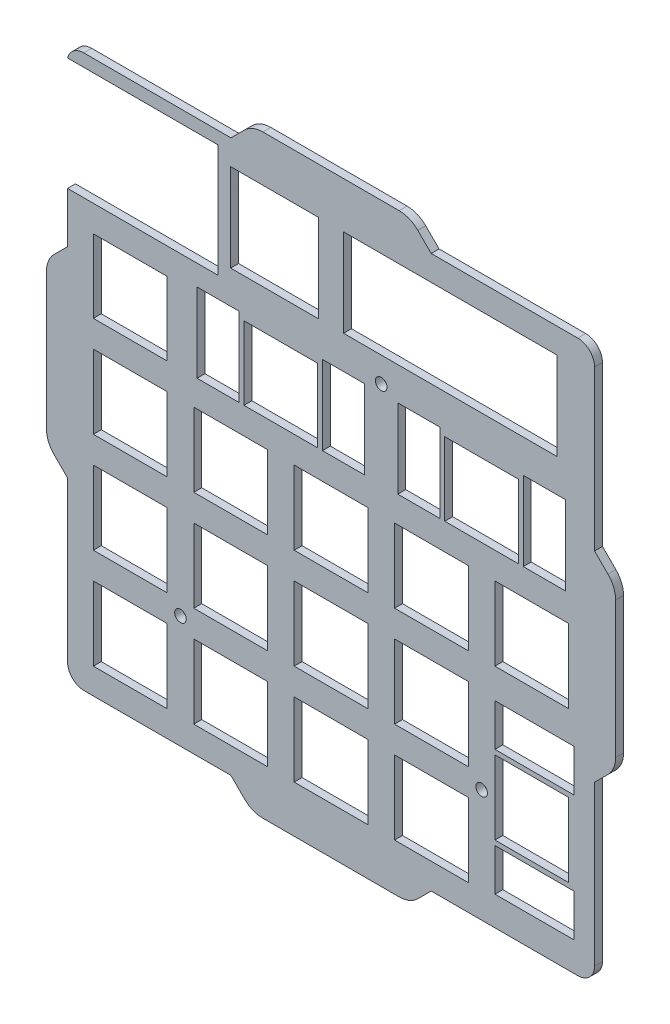
SolidWorks part; units mm, degrees
ref_plane "Front Plane" through (0, 0, 0) normal (1, 0, 0) x (0, 1, 0)
ref_plane "Top Plane" through (0, 0, 0) normal (0, 0, 1) x (0, 1, 0)
ref_plane "Right Plane" through (0, 0, 0) normal (0, 1, 0) x (-1, 0, 0)
sketch "Sketch2" plane through (0, 0, 0) normal (0, 0, 1) x (0, 1, 0)
  line L0 (0.0954, 95.5094) -> (76.2988, 95.5094) construction
  line L1 (76.2988, 95.5094) -> (76.2988, 76.4594) construction
  line L2 (76.2988, 0.2594) -> (0.0954, 0.2594) construction
  line L3 (0.0954, 0.2594) -> (0.0954, 95.5094) construction
  line L20 (12.1454, 16.7838) -> (12.1454, 2.7838)
  line L21 (12.1454, 2.7838) -> (26.1454, 2.7838)
  line L22 (26.1454, 2.7838) -> (26.1454, 16.7838)
  line L39 (26.1454, 16.7838) -> (12.1454, 16.7838)
  line L40 (40.7217, 16.7838) -> (54.7216, 16.7838)
  line L41 (54.7216, 16.7838) -> (54.7216, 2.7838)
  line L42 (54.7216, 2.7838) -> (40.7217, 2.7838)
  line L43 (40.7217, 2.7838) -> (40.7217, 16.7838)
  line L54 (59.7727, 26.3094) -> (59.7727, 12.3094)
  line L71 (59.7727, 12.3094) -> (73.6711, 12.3094)
  line L72 (73.6711, 12.3094) -> (73.6711, 26.3094)
  line L73 (73.6711, 26.3094) -> (59.7727, 26.3094)
  line L80 (2.6198, 35.8339) -> (16.62, 35.8339)
  line L81 (16.62, 35.8339) -> (16.62, 21.8347)
  line L82 (16.62, 21.8347) -> (2.6198, 21.8347)
  line L83 (2.6198, 21.8347) -> (2.6198, 35.8339)
  line L84 (21.6708, 35.8339) -> (35.6708, 35.8339)
  line L85 (35.6708, 35.8339) -> (35.6708, 21.8347)
  line L86 (35.6708, 21.8347) -> (21.6708, 21.8347)
  line L87 (21.6708, 21.8347) -> (21.6708, 35.8339)
  line L88 (40.7217, 35.8339) -> (54.7216, 35.8339)
  line L89 (54.7216, 35.8339) -> (54.7216, 21.8347)
  line L90 (54.7216, 21.8347) -> (40.7217, 21.8347)
  line L91 (40.7217, 21.8347) -> (40.7217, 35.8339)
  line L92 (2.6198, 54.8839) -> (16.62, 54.8839)
  line L93 (16.62, 54.8839) -> (16.62, 40.8849)
  line L94 (16.62, 40.8849) -> (2.6198, 40.8849)
  line L95 (2.6198, 40.8849) -> (2.6198, 54.8839)
  line L96 (21.6708, 54.8839) -> (35.6708, 54.8839)
  line L97 (35.6708, 54.8839) -> (35.6708, 40.8849)
  line L98 (35.6708, 40.8849) -> (21.6708, 40.8849)
  line L99 (21.6708, 40.8849) -> (21.6708, 54.8839)
  line L100 (40.7217, 54.8839) -> (54.7216, 54.8839)
  line L101 (54.7216, 54.8839) -> (54.7216, 40.8849)
  line L102 (54.7216, 40.8849) -> (40.7217, 40.8849)
  line L103 (40.7217, 40.8849) -> (40.7217, 54.8839)
  line L114 (59.7727, 64.4094) -> (59.7727, 50.4094)
  line L131 (59.7727, 50.4094) -> (73.6711, 50.4094)
  line L132 (73.6711, 50.4094) -> (73.6711, 64.4094)
  line L133 (73.6711, 64.4094) -> (59.7727, 64.4094)
  line L140 (2.6198, 73.9309) -> (16.62, 73.9309)
  line L141 (16.62, 73.9309) -> (16.62, 59.9368)
  line L142 (16.62, 59.9368) -> (2.6198, 59.9368)
  line L143 (2.6198, 59.9368) -> (2.6198, 73.9309)
  line L144 (21.6708, 73.9309) -> (35.6708, 73.9309)
  line L145 (35.6708, 73.9309) -> (35.6708, 59.9368)
  line L146 (35.6708, 59.9368) -> (21.6708, 59.9368)
  line L147 (21.6708, 59.9368) -> (21.6708, 73.9309)
  line L148 (40.7217, 73.9309) -> (54.7216, 73.9309)
  line L149 (54.7216, 73.9309) -> (54.7216, 59.9368)
  line L150 (54.7216, 59.9368) -> (40.7217, 59.9368)
  line L151 (40.7217, 59.9368) -> (40.7217, 73.9309)
  line L152 (2.6198, 92.9878) -> (16.62, 92.9878)
  line L153 (16.62, 92.9878) -> (16.62, 78.9878)
  line L154 (16.62, 78.9878) -> (2.6198, 78.9878)
  line L155 (2.6198, 78.9878) -> (2.6198, 92.9878)
  line L156 (21.6708, 92.9878) -> (35.6708, 92.9878)
  line L157 (35.6708, 92.9878) -> (35.6708, 78.9878)
  line L158 (35.6708, 78.9878) -> (21.6708, 78.9878)
  line L159 (21.6708, 78.9878) -> (21.6708, 92.9878)
  line L160 (40.7217, 92.9878) -> (54.7216, 92.9878)
  line L161 (54.7216, 92.9878) -> (54.7216, 78.9878)
  line L162 (54.7216, 78.9878) -> (40.7217, 78.9878)
  line L163 (40.7217, 78.9878) -> (40.7217, 92.9878)
  line L164 (59.7727, 92.9878) -> (73.6711, 92.9878)
  line L165 (73.6711, 92.9878) -> (73.6711, 78.9878)
  line L166 (73.6711, 78.9878) -> (59.7727, 78.9878)
  line L167 (59.7727, 78.9878) -> (59.7727, 92.9878)
  line L168 (76.2988, 95.5094) -> (102.4915, 95.5094) construction
  line L169 (76.2988, 0.2594) -> (102.4915, 0.2594) construction
  line L170 (102.4915, 0.2594) -> (102.4915, 95.5094) construction
  line L172 (19.1454, 95.5094) -> (19.1454, 0.2594) construction
  line L173 (0.0954, 76.4594) -> (76.2988, 76.4594) construction
  line L174 (0.0954, 57.4094) -> (76.2988, 57.4094) construction
  line L175 (0.0954, 38.3594) -> (76.2988, 38.3594) construction
  line L176 (0.0954, 19.3094) -> (76.2988, 19.3094) construction
  line L177 (38.1971, 95.5094) -> (38.1971, 0.2594) construction
  line L178 (57.2471, 95.5094) -> (57.2471, 0.2594) construction
  line L179 (76.2988, 45.5031) -> (81.0613, 45.5031) construction
  line L180 (81.0613, 66.9344) -> (97.73, 66.9344)
  line L181 (81.0613, 66.9344) -> (81.0613, 50.2656)
  line L182 (81.0613, 50.2656) -> (97.73, 50.2656)
  line L183 (97.73, 66.9344) -> (97.73, 50.2656)
  line L184 (81.0613, 45.5031) -> (81.0613, 5.0219)
  line L185 (81.0613, 5.0219) -> (97.73, 5.0219)
  line L186 (97.73, 5.0219) -> (97.73, 45.5031)
  line L187 (97.73, 45.5031) -> (81.0613, 45.5031)
  line L189 (78.68, 95.5094) -> (78.68, 69.3156)
  line L190 (78.68, 69.3156) -> (100.1103, 69.3156)
  line L191 (100.1103, 95.5636) -> (100.1103, 69.3156)
  line L194 (102.4915, 0.2594) -> (102.4915, 28.8844)
  line L195 (102.4915, 0.2594) -> (102.4915, -2.1219)
  line L196 (102.4915, -2.1219) -> (69.1029, -2.1219)
  line L197 (-2.2858, -2.1219) -> (-2.2858, 28.8844)
  line L198 (-2.2858, 97.8906) -> (31.1029, 97.8906)
  line L199 (78.68, 97.8906) -> (78.68, 95.5094)
  line L200 (100.1103, 95.5636) -> (100.1103, 97.8906)
  line L201 (100.1103, 97.8906) -> (102.4915, 97.8906)
  line L202 (102.4915, 97.8906) -> (102.4915, 95.5094)
  line L203 (35.0454, 1.7838) -> (27.0454, 1.7838)
  line L204 (3.2454, 16.7838) -> (11.2454, 16.7838)
  line L205 (3.2454, 16.7838) -> (3.2454, 1.7838)
  line L206 (3.2454, 1.7838) -> (11.2454, 1.7838)
  line L207 (11.2454, 16.7838) -> (11.2454, 1.7838)
  line L208 (27.0454, 16.7838) -> (27.0454, 1.7838)
  line L209 (35.0454, 16.7838) -> (27.0454, 16.7838)
  line L210 (35.0454, 16.7838) -> (35.0454, 1.7838)
  line L211 (59.7727, 35.2094) -> (74.7727, 35.2094)
  line L212 (59.7727, 11.4094) -> (74.7727, 11.4094)
  line L213 (59.7727, 11.4094) -> (59.7727, 3.4094)
  line L214 (59.7727, 3.4094) -> (74.7727, 3.4094)
  line L215 (74.7727, 11.4094) -> (74.7727, 3.4094)
  line L216 (74.7727, 27.2094) -> (74.7727, 35.2094)
  line L217 (59.7727, 27.2094) -> (74.7727, 27.2094)
  line L218 (59.7727, 27.2094) -> (59.7727, 35.2094)
  line L219 (59.7727, 41.5094) -> (74.7727, 41.5094)
  line L220 (59.7727, 65.3094) -> (74.7727, 65.3094)
  line L221 (59.7727, 65.3094) -> (59.7727, 73.3094)
  line L222 (59.7727, 73.3094) -> (74.7727, 73.3094)
  line L223 (74.7727, 65.3094) -> (74.7727, 73.3094)
  line L224 (74.7727, 49.5094) -> (74.7727, 41.5094)
  line L225 (59.7727, 49.5094) -> (74.7727, 49.5094)
  line L226 (59.7727, 49.5094) -> (59.7727, 41.5094)
  line L227 (7.2454, 16.7838) -> (19.1454, 16.7838) construction
  line L228 (59.7727, 7.4094) -> (59.7727, 19.3094) construction
  line L229 (59.7727, 57.4094) -> (59.7727, 69.3094) construction
  line L230 (76.2988, 38.3594) -> (76.2988, 0.2594) construction
  line L231 (76.2988, 76.4594) -> (76.2988, 38.3594) construction
  line L232 (50.1029, -2.1219) -> (50.1029, -6.1219) construction
  line L233 (63.0318, -6.1219) -> (37.1739, -6.1219)
  line L234 (66.5673, -4.6574) -> (69.1029, -2.1219)
  line L235 (33.6384, -4.6574) -> (31.1029, -2.1219)
  line L236 (31.1029, -2.1219) -> (-2.2858, -2.1219)
  line L237 (69.1029, -2.1219) -> (31.1029, -2.1219) construction
  line L238 (-2.2858, 47.8844) -> (102.4915, 47.8844) construction
  line L239 (50.1029, -2.1219) -> (50.1029, 97.8906) construction
  line L240 (50.1029, 97.8906) -> (50.1029, 101.8906) construction
  line L244 (31.1029, 97.8906) -> (69.1029, 97.8906) construction
  line L245 (69.1029, 97.8906) -> (78.68, 97.8906)
  line L246 (37.1739, 101.8906) -> (63.0318, 101.8906)
  line L247 (66.5673, 100.4261) -> (69.1029, 97.8906)
  line L248 (31.1029, 97.8906) -> (33.6384, 100.4261)
  line L249 (-2.2858, 47.8844) -> (-6.2858, 47.8844) construction
  line L250 (-6.2858, 60.8133) -> (-6.2858, 34.9554)
  line L251 (-4.8214, 31.4199) -> (-2.2858, 28.8844)
  line L252 (-4.8214, 64.3488) -> (-2.2858, 66.8844)
  line L253 (-2.2858, 28.8844) -> (-2.2858, 66.8844) construction
  line L254 (-2.2858, 66.8844) -> (-2.2858, 97.8906)
  line L255 (102.4915, 47.8844) -> (106.4915, 47.8844) construction
  line L256 (106.4915, 60.8133) -> (106.4915, 34.9554)
  line L257 (105.0271, 64.3488) -> (102.4915, 66.8844)
  line L258 (102.4915, 66.8844) -> (102.4915, 95.5094)
  line L260 (105.0271, 31.4199) -> (102.4915, 28.8844)
  arc A0 (-6.2858, 34.9554) -> (-4.8214, 31.4199) centre (-1.2858, 34.9554) ccw
  arc A1 (-6.2858, 60.8133) -> (-4.8214, 64.3488) centre (-1.2858, 60.8133) cw
  arc A2 (37.1739, 101.8906) -> (33.6384, 100.4261) centre (37.1739, 96.8906) ccw
  arc A3 (63.0318, 101.8906) -> (66.5673, 100.4261) centre (63.0318, 96.8906) cw
  arc A4 (106.4915, 60.8133) -> (105.0271, 64.3488) centre (101.4915, 60.8133) ccw
  arc A5 (106.4915, 34.9554) -> (105.0271, 31.4199) centre (101.4915, 34.9554) cw
  arc A6 (37.1739, -6.1219) -> (33.6384, -4.6574) centre (37.1739, -1.1219) cw
  arc A7 (63.0318, -6.1219) -> (66.5673, -4.6574) centre (63.0318, -1.1219) ccw
  circle A8 centre (19.1454, 76.4594) radius 1.1
  circle A9 centre (19.1454, 19.3094) radius 1.1
  circle A10 centre (76.2988, 38.3594) radius 1.1
  point P11 (19.1454, 16.7838)
  point P36 (7.2454, 16.7838)
  point P38 (59.7727, 19.3094)
  point P39 (59.7727, 7.4094)
  point P40 (59.7727, 69.3094)
  point P41 (59.7727, 57.4094)
  point P55 (50.1029, -2.1219)
  point P60 (50.1029, -6.1219)
  point P69 (50.1029, 101.8906)
  point P77 (-6.2858, 47.8844)
  point P107 (106.4915, 47.8844)
  point P113 (102.4915, 62.8844)
  point P127 (35.1029, -6.1219)
  point P130 (65.1029, -6.1219)
  point P133 (19.1454, 19.3094)
  point P139 (21.6708, 47.8844)
  point P190 (76.2988, 45.5031)
  point P205 (73.6711, 57.4094)
  point P206 (73.6711, 19.3094)
  dimension "D34" = 5
  dimension "D35" = 2.2
  dimension "D36" = 2.2
  dimension "D37" = 2.2
  dimension "D3" = 19.05
  dimension "D7" = 19.05
  dimension "D8" = 19.05
  dimension "D9" = 19.05
  dimension "D10" = 19.05
  dimension "D11" = 19.0517
  dimension "D5" = 19.05
  dimension "D6" = 19.05
  dimension "D2" = 26.1928
  dimension "D12" = 7.1437
  dimension "D13" = 4.7625
  dimension "D14" = 16.6687
  dimension "D4" = 16.6687
  dimension "D15" = 4.7625
  dimension "D16" = 2.3813
  dimension "D17" = 2.3813
  dimension "D18" = 2.3813
  dimension "D19" = 2.3813
  dimension "D20" = 2.3813
  dimension "D21" = 2.3813
  dimension "D22" = 7.1437
  dimension "D23" = 14
  dimension "D24" = 14
  dimension "D25" = 2.5244
  dimension "D26" = 14
  dimension "D28" = 8
  dimension "D27" = 11.9
  dimension "D29" = 15
  dimension "D32" = 30
  dimension "D33" = 4
  dimension "D30" = 225
  dimension "D31" = 225
extrude "Boss-Extrude1" add sketch "Sketch2" along normal blind 1.5
fillet "Fillet1" radius 3.175 4 edges at (-97.8906, 102.4915, 0.75) (-97.8906, -2.2858, 0.75) (2.1219, 102.4915, 0.75) (2.1219, -2.2858, 0.75)
equation "\"D19@Sketch2\"=2.38125"
equation "\"D20@Sketch2\"=2.38125"
equation "\"D21@Sketch2\"=2.38125"
